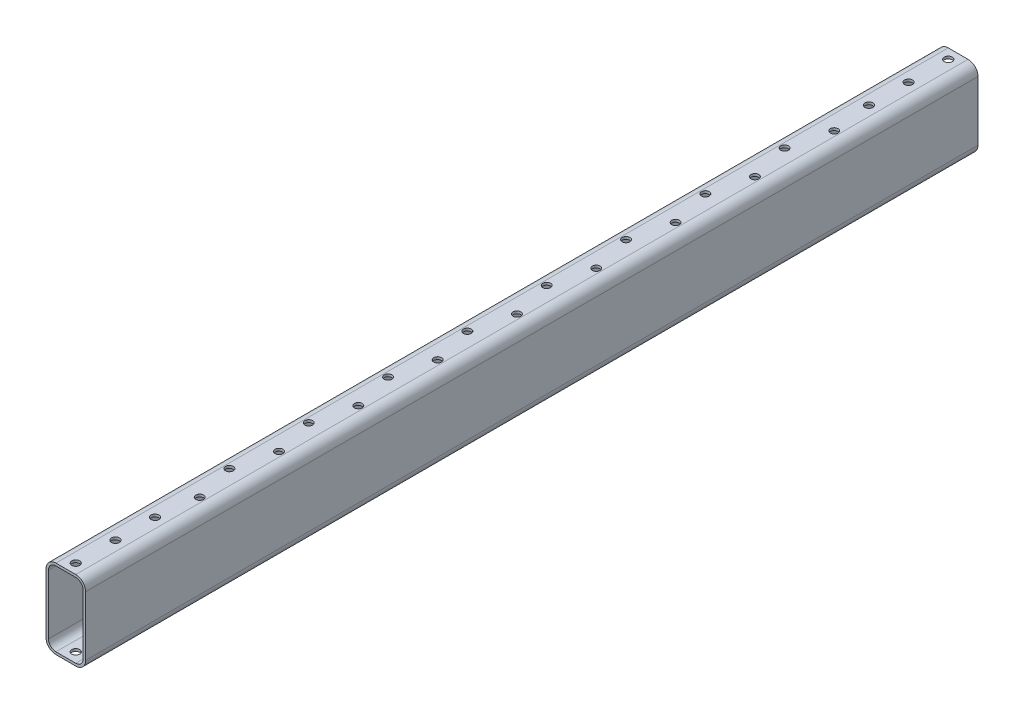
SolidWorks part; units mm, degrees
material "6061-T6 (SS)"
ref_plane "Front Plane" through (0, 0, 0) normal (0, 0, 1) x (1, 0, 0)
ref_plane "Top Plane" through (0, 0, 0) normal (0, 1, 0) x (1, 0, 0)
ref_plane "Right Plane" through (0, 0, 0) normal (1, 0, 0) x (0, 0, -1)
sketch "Sketch1" plane through (0, 0, 0) normal (0, 0, 1) x (1, 0, 0)
  line L1 (-6.35, -25.4) -> (6.35, -25.4)
  line L2 (-12.7, -19.05) -> (-12.7, 19.05)
  line L3 (-6.35, 25.4) -> (6.35, 25.4)
  line L4 (12.7, -19.05) -> (12.7, 19.05)
  line L5 (-12.7, -25.4) -> (12.7, 25.4) construction
  line L6 (-12.7, 25.4) -> (12.7, -25.4) construction
  arc A0 (-12.7, -19.05) -> (-6.35, -25.4) centre (-6.35, -19.05) ccw
  arc A1 (6.35, -25.4) -> (12.7, -19.05) centre (6.35, -19.05) ccw
  arc A2 (6.35, 25.4) -> (12.7, 19.05) centre (6.35, 19.05) cw
  arc A3 (-12.7, 19.05) -> (-6.35, 25.4) centre (-6.35, 19.05) cw
  point P0 (0, 0)
  dimension "D3" = 6.35
  dimension "D1" = 50.8
  dimension "D2" = 25.4
extrude "Extrude-Thin1" add sketch "Sketch1" along normal blind 571.5 thin thin type one direction reverse wall 1.5875
hole_wizard "#10 Clearance Hole1" positions "3DSketch1" profile "Sketch3" hole size "#10" standard "ANSI Inch" end condition through all
sketch3d "3DSketch1"
  line L1 (6.35, 25.4, 0) -> (-6.35, 25.4, 0) construction
  line L6 (0, 25.4, 571.5) -> (0, 25.4, 0) construction
  line L7 (6.35, 25.4, 571.5) -> (-6.35, 25.4, 571.5) construction
  point P57 (0, 25.4, 6.35)
  point P59 (0, 25.4, 31.75)
  point P61 (0, 25.4, 57.15)
  point P63 (0, 25.4, 539.75)
  point P65 (0, 25.4, 514.35)
  point P67 (0, 25.4, 565.15)
  dimension "D1" = 25.4
  dimension "D2" = 25.4
  dimension "D3" = 6.35
  dimension "D4" = 25.4
  dimension "D5" = 25.4
  dimension "D6" = 6.35
sketch "Sketch3" plane through (0, 25.4, 565.15) normal (1, 0, 0) x (0, 0, 1)
  line L0 (0, 0) -> (0, 50.8)
  line L1 (0, 50.8) -> (2.5527, 50.8)
  line L2 (2.5527, 50.8) -> (2.5527, 0)
  line L5 (2.5527, 0) -> (0, 0)
  line L11 (0, -6.35) -> (0, 107.95) construction
  dimension "Thru Hole Dia." = 5.1054
  dimension "Thru Hole Depth" = 50.8
hole_wizard "3/16 (0.195) Diameter Hole1" positions "Sketch4" profile "Sketch5" hole size "3/16" standard "ANSI Inch" end condition up to next
sketch "Sketch4" plane through (0, 25.4, 0) normal (0, 1, 0) x (1, 0, 0)
  point P78 (-3.175, -107.95)
  point P81 (3.175, -82.55)
  point P84 (3.175, -133.35)
  point P102 (-3.175, -158.75)
  point P105 (3.175, -184.15)
  point P108 (-3.175, -209.55)
  point P111 (3.175, -234.95)
  point P114 (-3.175, -260.35)
  point P117 (3.175, -285.75)
  point P120 (-3.175, -311.15)
  point P123 (3.175, -336.55)
  point P126 (-3.175, -361.95)
  point P129 (3.175, -387.35)
  point P132 (-3.175, -412.75)
  point P135 (3.175, -438.15)
  point P138 (-3.175, -463.55)
  point P141 (3.175, -488.95)
sketch "Sketch5" plane through (-3.175, 25.4, 107.95) normal (1, 0, 0) x (0, 0, 1)
  line L0 (0, 0) -> (0, 1.5875)
  line L1 (0, 1.5875) -> (2.4765, 1.5875)
  line L2 (2.4765, 1.5875) -> (2.4765, 0)
  line L5 (2.4765, 0) -> (0, 0)
  line L11 (0, -6.35) -> (0, 107.95) construction
  dimension "Thru Hole Dia." = 4.953
  dimension "Thru Hole Depth" = 1.5875
